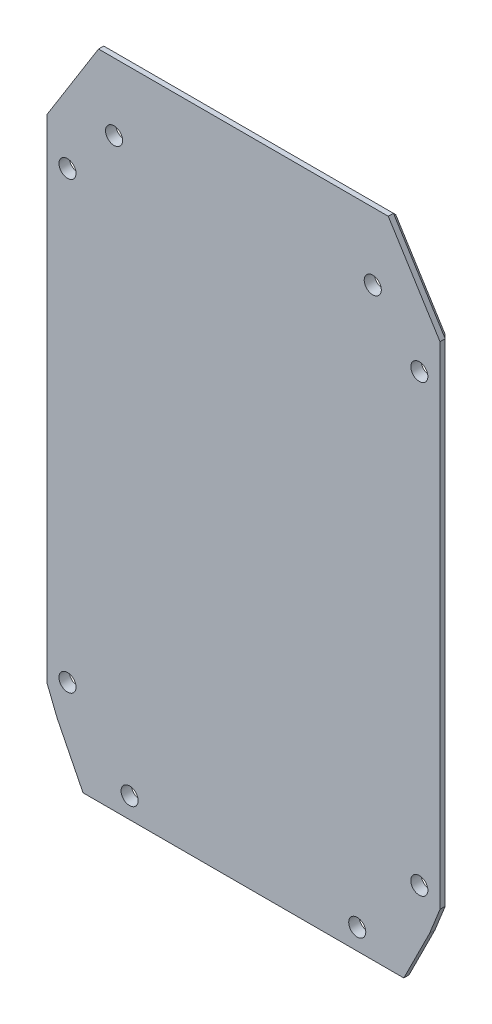
SolidWorks part; units mm, degrees
material "镁合金_CNC_暂定1800kg_m3"
ref_plane "前视基准面" through (0, 0, 0) normal (0, 0, 1) x (1, 0, 0)
ref_plane "上视基准面" through (0, 0, 0) normal (0, 1, 0) x (1, 0, 0)
ref_plane "右视基准面" through (0, 0, 0) normal (1, 0, 0) x (0, 0, -1)
other "Configuration Table"
sketch "草图3" plane through (0, 0, 0) normal (0, 0, 1) x (1, 0, 0)
  line L20 (-31, -60) -> (31, -60)
  line L21 (31, -60) -> (36, -50)
  line L22 (36, -50) -> (38, -45)
  line L23 (38, -45) -> (38, 50)
  line L24 (38, 50) -> (28, 66)
  line L25 (28, 66) -> (-28, 66)
  line L26 (-28, 66) -> (-38, 50)
  line L27 (-38, 50) -> (-38, -45)
  line L28 (-38, -45) -> (-36, -50)
  line L29 (-36, -50) -> (-31, -60)
  circle A24 centre (-22, -56) radius 1.65
  circle A25 centre (-25, 53) radius 1.65
  circle A26 centre (-34, -43) radius 1.65
  circle A27 centre (-34, 43) radius 1.65
  circle A28 centre (22, -56) radius 1.65
  circle A29 centre (25, 53) radius 1.65
  circle A30 centre (34, -43) radius 1.65
  circle A31 centre (34, 43) radius 1.65
extrude "两毫米镁合金检修底盖" add sketch "草图3" along normal blind 2
chamfer "底盖全周向心倒角_C1" distance 1 angle 45 10 edges at (-33.5, -55, 0) (0, -60, 0) (33.5, -55, 0) (37, -47.5, 0) (38, 2.5, 0) (33, 58, 0) (0, 66, 0) (-33, 58, 0) (-38, 2.5, 0) (-37, -47.5, 0)
